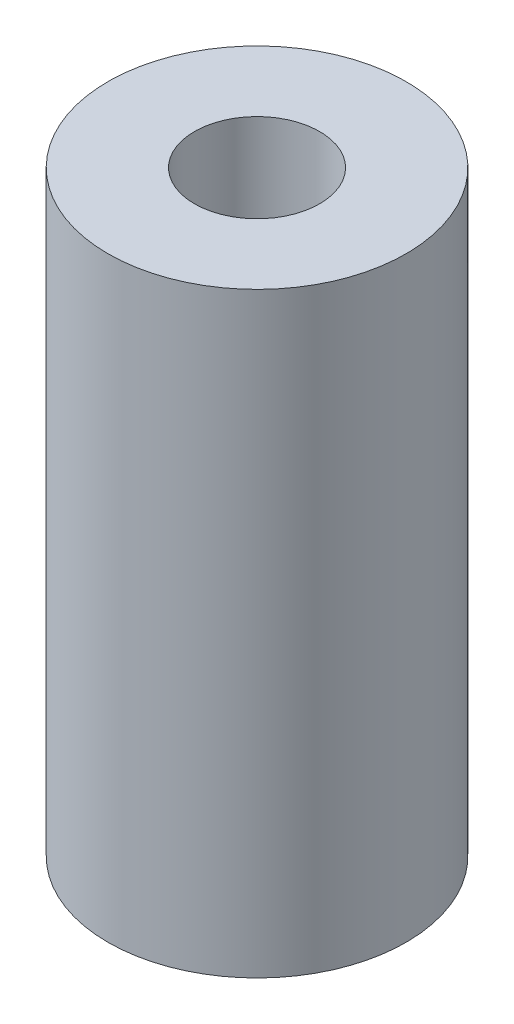
SolidWorks part; units mm, degrees
material "ABS"
ref_plane "Front Plane" through (0, 0, 0) normal (0, 0, 1) x (1, 0, 0)
ref_plane "Top Plane" through (0, 0, 0) normal (0, 1, 0) x (1, 0, 0)
ref_plane "Right Plane" through (0, 0, 0) normal (1, 0, 0) x (0, 0, -1)
sketch "Sketch1" plane through (0, 0, 0) normal (0, 1, 0) x (1, 0, 0)
  circle A0 centre (0, 0) radius 6.35
  circle A1 centre (0, 0) radius 2.667
  dimension "D1" = 12.7
  dimension "D2" = 5.334
extrude "Boss-Extrude1" add sketch "Sketch1" along normal blind 25.4
sketch "Sketch2" plane through (0, 0, 0) normal (0, -1, 0) x (-1, 0, 0)
  circle A0 centre (0, 0) radius 9.525
  circle A1 centre (0, 0) radius 2.54
  dimension "D1" = 19.05
extrude "Boss-Extrude2" [suppressed] add sketch "Sketch2" against normal blind 7.62
chamfer "Chamfer1" [suppressed] distance 3.175 angle 68
fillet "Fillet1" [suppressed] radius 12.7
sketch "Sketch3" plane through (0, 25.4, 0) normal (0, 1, 0) x (1, 0, 0)
  circle A0 centre (0, 0) radius 9.525
  circle A1 centre (0, 0) radius 2.54
  dimension "D1" = 19.05
extrude "Boss-Extrude3" [suppressed] add sketch "Sketch3" against normal blind 7.62
chamfer "Chamfer2" [suppressed] distance 3.175 angle 68
fillet "Fillet2" [suppressed] radius 12.7
sketch "Sketch4" plane through (0, 0, 0) normal (0, 0, 1) x (1, 0, 0)
  line L1 (-14.5993, 37.9681) -> (14.5993, 37.9681)
  line L2 (-14.5993, 37.9681) -> (-14.5993, -4.7123)
  line L3 (-14.5993, -4.7123) -> (14.5993, -4.7123)
  line L4 (14.5993, 37.9681) -> (14.5993, -4.7123)
  line L5 (-14.5993, 37.9681) -> (14.5993, -4.7123) construction
  line L6 (-14.5993, -4.7123) -> (14.5993, 37.9681) construction
  point P0 (0, 16.6279)
extrude "Cut-Extrude1" [suppressed] cut sketch "Sketch4" along normal through all from offset 6.35
